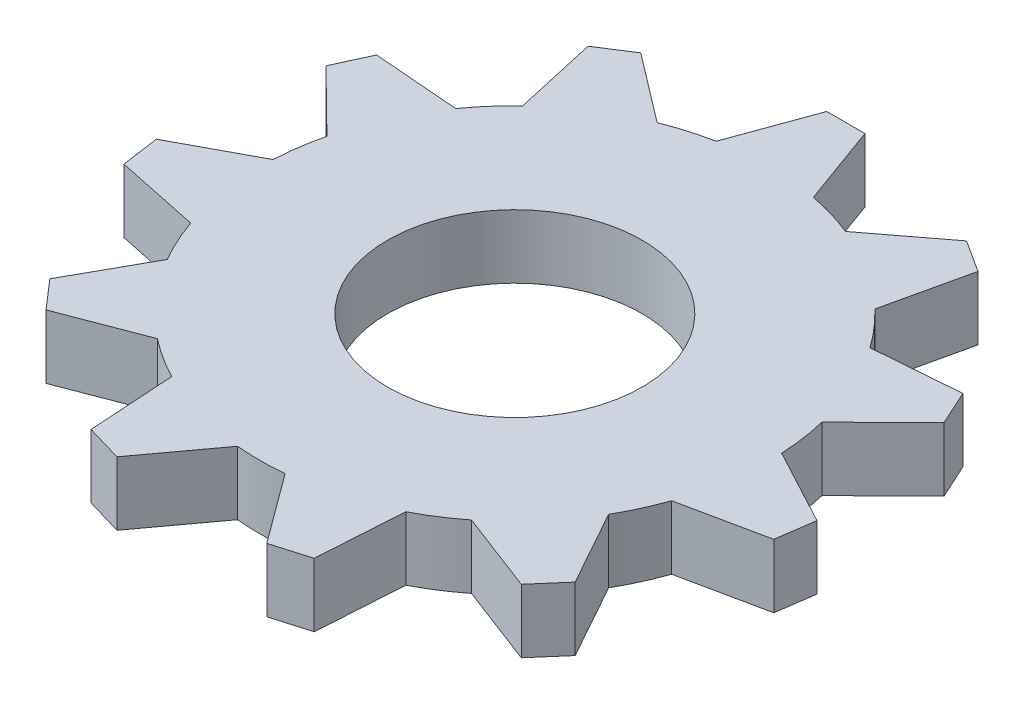
SolidWorks part; units mm, degrees
ref_plane "Front Plane" through (0, 0, 0) normal (0, 0, 1) x (1, 0, 0)
ref_plane "Top Plane" through (0, 0, 0) normal (0, 1, 0) x (1, 0, 0)
ref_plane "Right Plane" through (0, 0, 0) normal (1, 0, 0) x (0, 0, -1)
sketch "Sketch1" plane through (0, 0, 0) normal (0, 1, 0) x (1, 0, 0)
  circle A0 centre (0, 0) radius 20
  dimension "D1" = 40
extrude "Boss-Extrude1" add sketch "Sketch1" along normal blind 5
sketch "Sketch2" plane through (0, 5, 0) normal (0, 1, 0) x (1, 0, 0)
  line L0 (0, 0) -> (0, 31.7443) construction
  line L1 (-1.5, 26) -> (1.5, 26)
  line L2 (1.5, 26) -> (3.8177, 19.6323)
  line L3 (0, 26) -> (0, 20)
  line L4 (-1.5, 26) -> (-3.8177, 19.6323)
  line L5 (-3.8177, 19.6323) -> (3.8177, 19.6323)
  line L6 (7.4024, 18.5797) -> (13.8256, 14.4517)
  line L7 (15.3185, 21.0616) -> (13.8256, 14.4517)
  line L8 (12.7948, 22.6836) -> (15.3185, 21.0616)
  line L9 (12.7948, 22.6836) -> (7.4024, 18.5797)
  line L10 (16.2722, 11.6282) -> (19.444, 4.6829)
  line L11 (24.2736, 9.4363) -> (19.444, 4.6829)
  line L12 (23.0273, 12.1652) -> (24.2736, 9.4363)
  line L13 (23.0273, 12.1652) -> (16.2722, 11.6282)
  line L14 (19.9757, 0.9849) -> (18.8891, -6.5728)
  line L15 (25.5219, -5.1849) -> (18.8891, -6.5728)
  line L16 (25.9488, -2.2155) -> (25.5219, -5.1849)
  line L17 (25.9488, -2.2155) -> (19.9757, 0.9849)
  line L18 (17.3371, -9.9712) -> (12.337, -15.7416)
  line L19 (18.6672, -18.16) -> (12.337, -15.7416)
  line L20 (20.6318, -15.8928) -> (18.6672, -18.16)
  line L21 (20.6318, -15.8928) -> (17.3371, -9.9712)
  line L22 (9.1941, -17.7614) -> (1.868, -19.9126)
  line L23 (5.8858, -25.3694) -> (1.868, -19.9126)
  line L24 (8.7643, -24.5242) -> (5.8858, -25.3694)
  line L25 (8.7643, -24.5242) -> (9.1941, -17.7614)
  line L26 (-1.868, -19.9126) -> (-9.1941, -17.7614)
  line L27 (-8.7643, -24.5242) -> (-9.1941, -17.7614)
  line L28 (-5.8858, -25.3694) -> (-8.7643, -24.5242)
  line L29 (-5.8858, -25.3694) -> (-1.868, -19.9126)
  line L30 (-12.337, -15.7416) -> (-17.3371, -9.9712)
  line L31 (-20.6318, -15.8928) -> (-17.3371, -9.9712)
  line L32 (-18.6672, -18.16) -> (-20.6318, -15.8928)
  line L33 (-18.6672, -18.16) -> (-12.337, -15.7416)
  line L34 (-18.8891, -6.5728) -> (-19.9757, 0.9849)
  line L35 (-25.9488, -2.2155) -> (-19.9757, 0.9849)
  line L36 (-25.5219, -5.1849) -> (-25.9488, -2.2155)
  line L37 (-25.5219, -5.1849) -> (-18.8891, -6.5728)
  line L38 (-19.444, 4.6829) -> (-16.2722, 11.6282)
  line L39 (-23.0273, 12.1652) -> (-16.2722, 11.6282)
  line L40 (-24.2736, 9.4363) -> (-23.0273, 12.1652)
  line L41 (-24.2736, 9.4363) -> (-19.444, 4.6829)
  line L42 (-13.8256, 14.4517) -> (-7.4024, 18.5797)
  line L43 (-12.7948, 22.6836) -> (-7.4024, 18.5797)
  line L44 (-15.3185, 21.0616) -> (-12.7948, 22.6836)
  line L45 (-15.3185, 21.0616) -> (-13.8256, 14.4517)
  circle A0 centre (0, 0) radius 20 construction
  circle M6 centre (0, 0) radius 20
  dimension "D1" = 6
  dimension "D2" = 110
  dimension "D3" = 1.5
  dimension "D4" = 11
extrude "Boss-Extrude2" add sketch "Sketch2" against normal blind 5 contours L44 L45 L43 M6 | L40 L41 L39 M6 | L36 L37 L35 M6 | L32 L33 L31 M6 | L28 L29 L27 M6 | L24 L25 L23 M6 | L20 L21 L19 M6 | L16 L17 L15 M6 | L12 L13 L11 M6 | L8 L9 L7 M6 | L1 L4 L3 M6 | L1 L3 L2 M6 region at (-1.4124, 5, -22.5045) region at (1.4124, 5, -22.5045) region at (-12.1668, 5, -18.932) region at (12.1668, 5, -18.932) region at (-20.4708, 5, -9.3487) region at (20.4708, 5, -9.3487) region at (-22.2754, 5, 3.2027) region at (22.2754, 5, 3.2027) region at (-17.0078, 5, 14.7373) region at (17.0078, 5, 14.7373) region at (-6.3402, 5, 21.5929) region at (6.3402, 5, 21.5929)
sketch "Sketch3" plane through (0, 5, 0) normal (0, 1, 0) x (1, 0, 0)
  circle A0 centre (0, 0) radius 10
  dimension "D1" = 20
extrude "Cut-Extrude1" cut sketch "Sketch3" against normal blind 5
